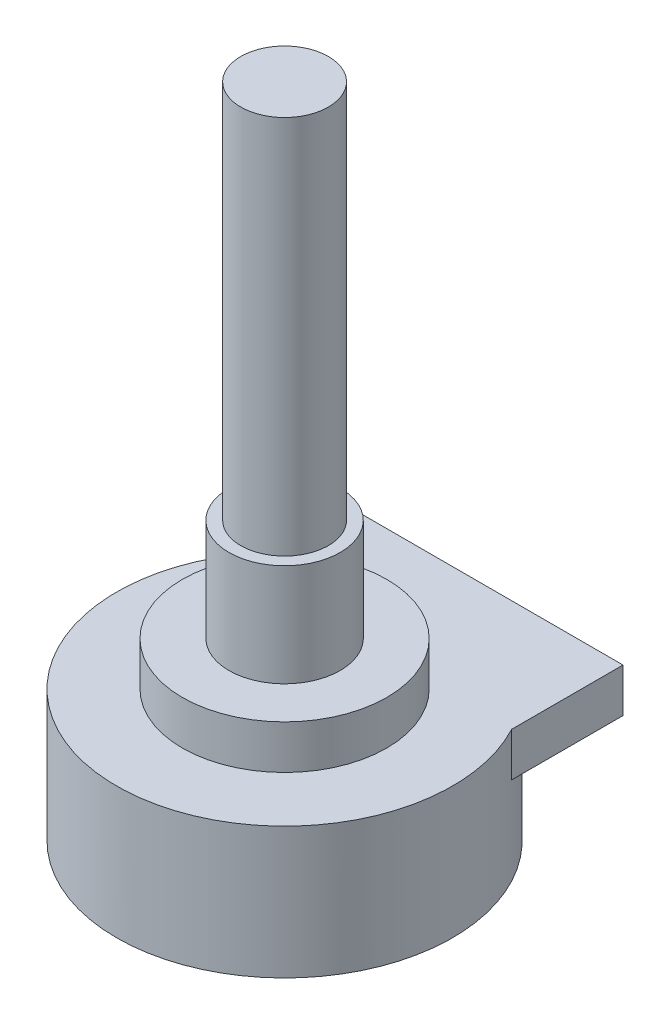
SolidWorks part; units mm, degrees
ref_plane "Front Plane" through (0, 0, 0) normal (0, 0, 1) x (1, 0, 0)
ref_plane "Top Plane" through (0, 0, 0) normal (0, 1, 0) x (1, 0, 0)
ref_plane "Right Plane" through (0, 0, 0) normal (1, 0, 0) x (0, 0, -1)
sketch "Sketch1" plane through (0, 0, 0) normal (0, 1, 0) x (1, 0, 0)
  line L0 (1.1176, 8.7884) -> (1.1176, -34.6964) construction
  line L1 (-9.0424, 8.7884) -> (11.2776, 8.7884)
  line L2 (-9.0424, 8.7884) -> (-9.0424, 1.1684)
  line L4 (11.2776, 8.7884) -> (11.2776, 1.1684)
  arc A0 (-9.0424, 1.1684) -> (11.2776, 1.1684) centre (1.1176, -4.219) ccw
  circle A1 centre (1.1176, -4.219) radius 3.81
  circle A2 centre (1.1176, -4.219) radius 3
  circle A3 centre (1.1176, -4.219) radius 7
  dimension "D1" = 20.32
  dimension "D2" = 7.62
extrude "Boss-Extrude1" add sketch "Sketch1" along normal blind 9 contours L0 L1 L2 A0 A3 | L1 L0 A3 A0 L4 region at (6.1976, 0, -8.5177) region at (0.8469, 0, -5.7847)
extrude "Boss-Extrude2" add sketch "Sketch1<3>" along normal blind 12 contours L0 A3 A1 | A3 L0 A1 region at (5.9567, 0, -0.62) region at (0.9611, 0, -1.186)
sketch "Sketch1<3>" plane through (0, 0, 0) normal (0, 1, 0) x (1, 0, 0) same geometry as "Sketch1"
extrude "Boss-Extrude3" add sketch "Sketch1<4>" along normal blind 19 contours L0 A1 A2 | A1 L0 A2 region at (3.7514, 0, 1.5852) region at (1.0324, 0, 0.814)
sketch "Sketch1<4>" plane through (0, 0, 0) normal (0, 1, 0) x (1, 0, 0) same geometry as "Sketch1"
extrude "Boss-Extrude4" add sketch "Sketch1<5>" along normal blind 45 contours L0 A2 | A2 L0 region at (2.3908, 0, 4.219) region at (-0.1556, 0, 4.219)
sketch "Sketch1<5>" plane through (0, 0, 0) normal (0, 1, 0) x (1, 0, 0) same geometry as "Sketch1"
sketch "Sketch2" plane through (0, 0, 0) normal (0, -1, 0) x (-1, 0, 0)
  line L0 (-1.1176, -15.719) -> (-1.1176, 8.7884) construction
  line L1 (9.0424, 8.7884) -> (-11.2776, 8.7884) construction
  line L2 (10.3824, -4.219) -> (-12.6176, -4.219) construction
  line L3 (-11.2776, 8.7884) -> (-11.2776, 1.1684) construction
  line L4 (9.0424, 1.1684) -> (9.0424, 8.7884)
  line L5 (9.0424, 8.7884) -> (-11.2776, 8.7884)
  line L6 (-11.2776, 8.7884) -> (-11.2776, 1.1684)
  arc A0 (-11.2776, 1.1684) -> (9.0424, 1.1684) centre (-1.1176, -4.219) ccw construction
  arc A1 (9.0424, 1.1684) -> (-11.2776, 1.1684) centre (-1.1176, -4.219) ccw
extrude "Cut-Extrude1" cut sketch "Sketch2" against normal blind 6
